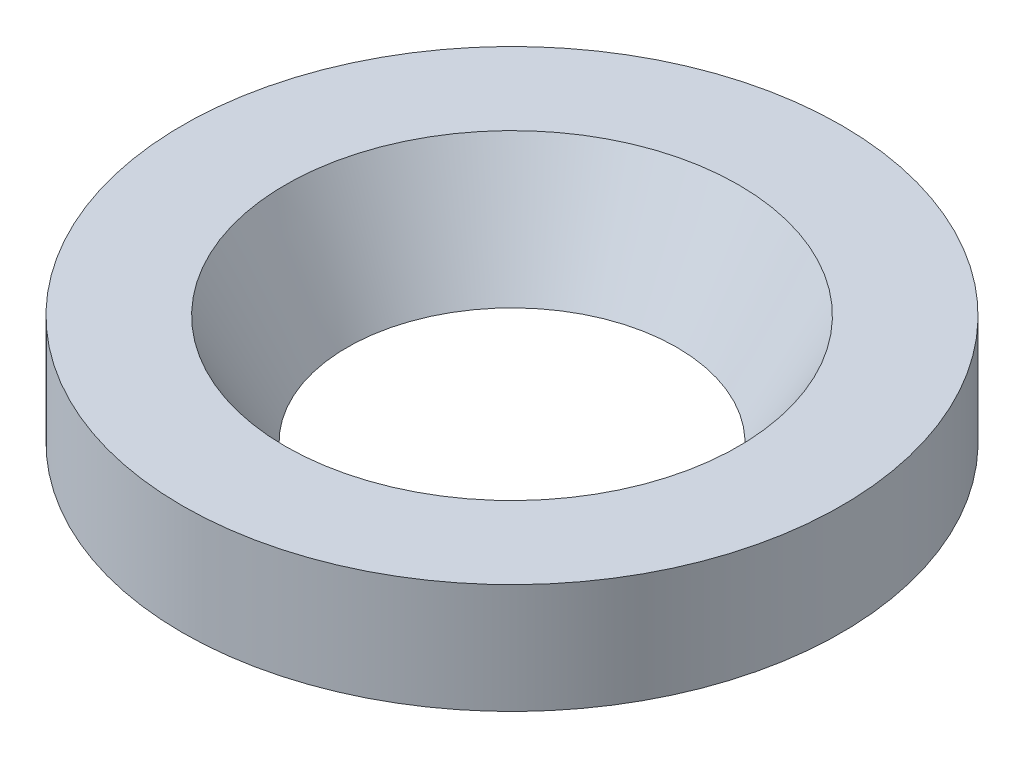
SolidWorks part; units mm, degrees
material "6061 Alloy"
ref_plane "Front Plane" through (0, 0, 0) normal (0, 0, 1) x (1, 0, 0)
ref_plane "Top Plane" through (0, 0, 0) normal (0, 1, 0) x (1, 0, 0)
ref_plane "Right Plane" through (0, 0, 0) normal (1, 0, 0) x (0, 0, -1)
sketch "Sketch1" plane through (0, 0, 0) normal (0, 1, 0) x (1, 0, 0)
  circle A0 centre (0, 0) radius 3
  circle A1 centre (0, 0) radius 6
  dimension "D1" = 6
  dimension "D2" = 12
extrude "Boss-Extrude1" add sketch "Sketch1" along normal blind 2
chamfer "Chamfer1" distance 1.125 distance2 2 1 edges at (0, 2, 3) first distance on face at (0, 2, 6)
